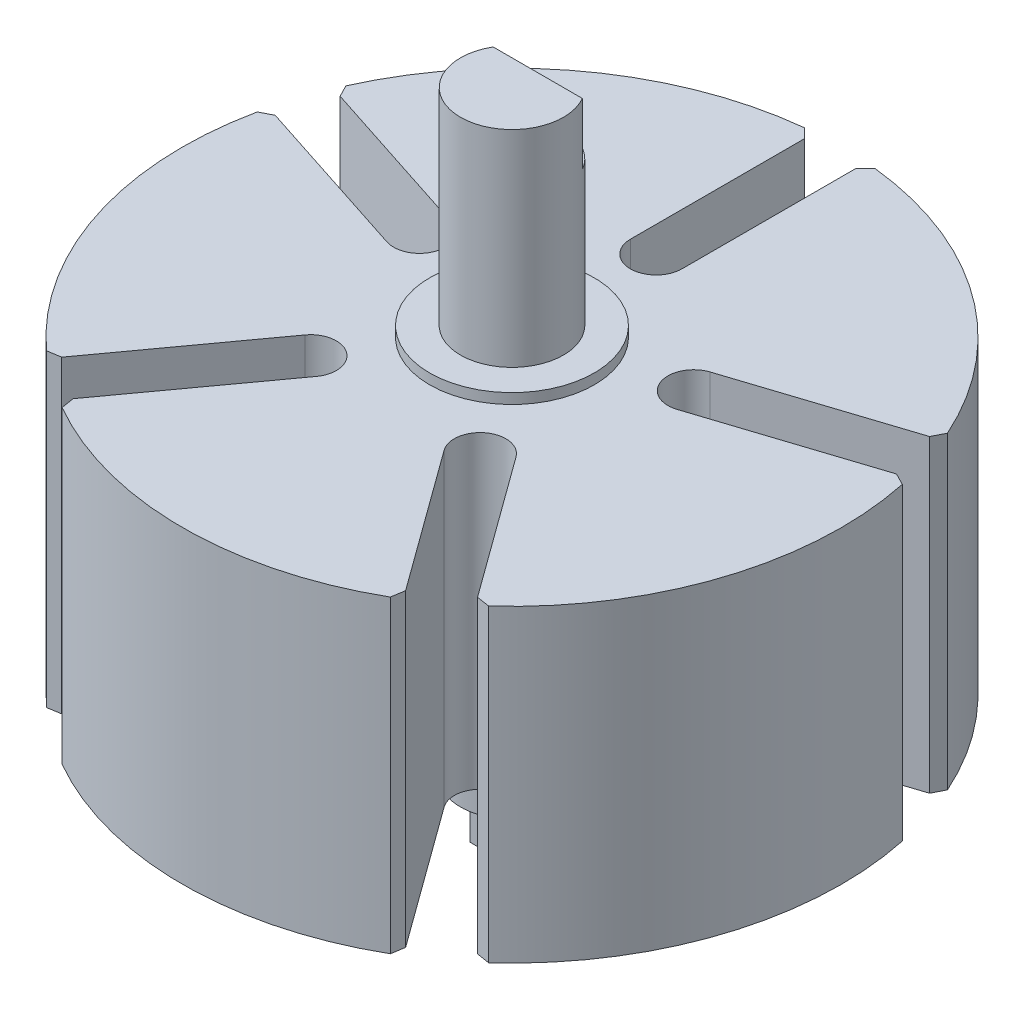
SolidWorks part; units mm, degrees
ref_plane "前视基准面" through (0, 0, 0) normal (0, 0, 1) x (1, 0, 0)
ref_plane "上视基准面" through (0, 0, 0) normal (0, 1, 0) x (1, 0, 0)
ref_plane "右视基准面" through (0, 0, 0) normal (1, 0, 0) x (0, 0, -1)
sketch "草图1" plane through (0, 0, 0) normal (0, 1, 0) x (1, 0, 0)
  circle A0 centre (0, 0) radius 16
  dimension "D1" = 32
extrude "凸台-拉伸1" add sketch "草图1" along normal blind 15
sketch "草图2" plane through (0, 15, 0) normal (0, 1, 0) x (1, 0, 0)
  circle A0 centre (0, 0) radius 4
  dimension "D1" = 8
extrude "凸台-拉伸2" add sketch "草图2" along normal blind 0.5
sketch "草图3" plane through (0, 0, 0) normal (0, -1, 0) x (1, 0, 0)
  circle A0 centre (0, 0) radius 4
  dimension "D1" = 8
extrude "凸台-拉伸3" add sketch "草图3" along normal blind 0.5
sketch "草图4" plane through (0, 15.5, 0) normal (0, 1, 0) x (1, 0, 0)
  circle A0 centre (0, 0) radius 2.5
  dimension "D1" = 5
extrude "凸台-拉伸4" add sketch "草图4" along normal blind 10
sketch "草图5" plane through (0, -0.5, 0) normal (0, -1, 0) x (1, 0, 0)
  circle A0 centre (0, 0) radius 2.5
  dimension "D1" = 5
extrude "凸台-拉伸5" add sketch "草图5" along normal blind 3
sketch "草图6" plane through (0, 25.5, 0) normal (0, 1, 0) x (1, 0, 0)
  line L0 (-2.1651, 1.25) -> (2.1651, 1.25)
  line L1 (-2.1651, 1.25) -> (0, 0) construction
  line L2 (0, 0) -> (2.1651, 1.25) construction
  circle A0 centre (0, 0) radius 2.5 construction
  circle A2 centre (0, 0) radius 2.5
  arc A3 (2.1651, 1.25) -> (-2.1651, 1.25) centre (0, 0) ccw
  dimension "D1" = 120
  dimension "D2" = 0
extrude "切除-拉伸1" cut sketch "草图6" against normal blind 3
sketch "草图7" plane through (0, 15, 0) normal (0, 1, 0) x (1, 0, 0)
  line L0 (0, 0) -> (0, 16.218) construction
  line L1 (-1.25, 7) -> (-1.25, 19)
  line L2 (-1.25, 19) -> (1.25, 19)
  line L3 (1.25, 19) -> (1.25, 7)
  line L4 (0, 16) -> (2.9481, 16) construction
  circle A0 centre (0, 7) radius 1.25 construction
  circle A2 centre (0, 0) radius 16 construction
  arc A3 (1.25, 7) -> (-1.25, 7) centre (0, 7) cw
  dimension "D1" = 2.5
  dimension "D2" = 3
  dimension "D3" = 7
extrude "切除-拉伸2" cut sketch "草图7" against normal through all
pattern_circular "阵列(圆周)1" count 5 over 360 about axis through (0, 25.5, 0) along (0, -1, 0) of "切除-拉伸2" reverse direction yes
sketch "草图8" plane through (0, -3.5, 0) normal (0, -1, 0) x (1, 0, 0)
  circle A0 centre (0, 0) radius 1.5
  dimension "D1" = 3
extrude "凸台-拉伸6" add sketch "草图8" along normal blind 3
chamfer "倒角1" distance 0.5 angle 45 10 edges at (-15.5567, 7.5, -3.7403) (-14.7841, 7.5, -6.118) (-10.3871, 7.5, 12.17) (-8.3645, 7.5, 13.6394) (8.3645, 7.5, 13.6394) (10.3871, 7.5, 12.17) (15.5567, 7.5, -3.7403) (14.7841, 7.5, -6.118) (1.25, 7.5, -15.9511) (-1.25, 7.5, -15.9511) first distance on face at (-11.3002, 7.5, -2.3573) first distance on face at (-10.5276, 7.5, -4.735) first distance on face at (-7.7564, 7.5, 8.5492) first distance on face at (-5.7339, 7.5, 10.0186) first distance on face at (5.7339, 7.5, 10.0186) first distance on face at (7.7564, 7.5, 8.5492) first distance on face at (11.3002, 7.5, -2.3573) first distance on face at (10.5276, 7.5, -4.735) first distance on face at (1.25, 7.5, -11.4755) first distance on face at (-1.25, 7.5, -11.4755)
sketch "草图9" plane through (0, -6.5, 0) normal (0, -1, 0) x (1, 0, 0)
  line L0 (-1.299, 0.75) -> (1.299, 0.75)
  line L1 (0, 0) -> (-1.299, 0.75) construction
  line L2 (1.299, 0.75) -> (0, 0) construction
  circle A0 centre (0, 0) radius 1.5 construction
  arc A1 (1.299, 0.75) -> (-1.299, 0.75) centre (0, 0) ccw
  dimension "D1" = 120
extrude "切除-拉伸3" cut sketch "草图9" against normal blind 3
